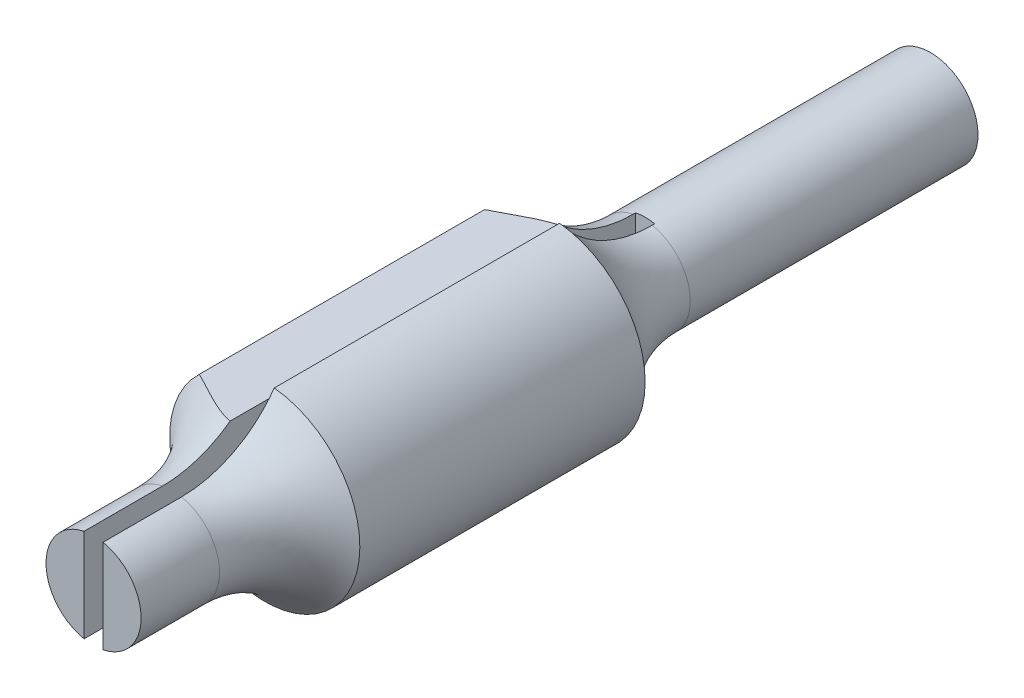
SolidWorks part; units mm, degrees
ref_plane "前视基准面" through (0, 0, 0) normal (0, 0, 1) x (1, 0, 0)
ref_plane "上视基准面" through (0, 0, 0) normal (0, 1, 0) x (1, 0, 0)
ref_plane "右视基准面" through (0, 0, 0) normal (1, 0, 0) x (0, 0, -1)
other "Configuration Table"
sketch "草图4" plane through (0, 0, 0) normal (0, 0, 1) x (1, 0, 0)
  circle A0 centre (0, 0) radius 5
  dimension "D1" = 10
extrude "凸台-拉伸2" add sketch "草图4" along normal blind 15
sketch "草图6" plane through (0, 0, 0) normal (0, 0, -1) x (-1, 0, 0)
  circle A0 centre (0, 0) radius 2.5
  dimension "D1" = 5
extrude "凸台-拉伸3" add sketch "草图6" along normal blind 20
sketch "草图7" plane through (0, 0, 15) normal (0, 0, 1) x (1, 0, 0)
  circle A0 centre (0, 0) radius 2.5
  dimension "D1" = 5
extrude "凸台-拉伸4" add sketch "草图7" along normal blind 9
sketch "草图5" plane through (0, 0, 0) normal (0, 0, -1) x (-1, 0, 0)
  line L0 (0, 0) -> (0, 5) construction
  line L1 (0.5, 3.628) -> (3.4405, 3.628)
  line L2 (-0.5, -2.9219) -> (0.5, -2.9219)
  line L3 (-0.5, -2.9219) -> (-0.5, 4.1248)
  line L5 (0.5, -2.9219) -> (0.5, 3.628)
  line L6 (-0.5, 4.1248) -> (-0.5, 4.9749)
  circle A0 centre (0, 0) radius 5 construction
  arc A1 (-0.5, 4.9749) -> (3.4405, 3.628) centre (0, 0) cw
  dimension "D1" = 1
  dimension "D2" = 0.5
extrude "切除-拉伸1" cut sketch "草图5" against normal blind 74 and the other way blind 5
fillet "圆角1" radius 6 1 edges at (2.5, 0, 0)
fillet "圆角2" radius 6 1 edges at (2.5, 0, 15)
